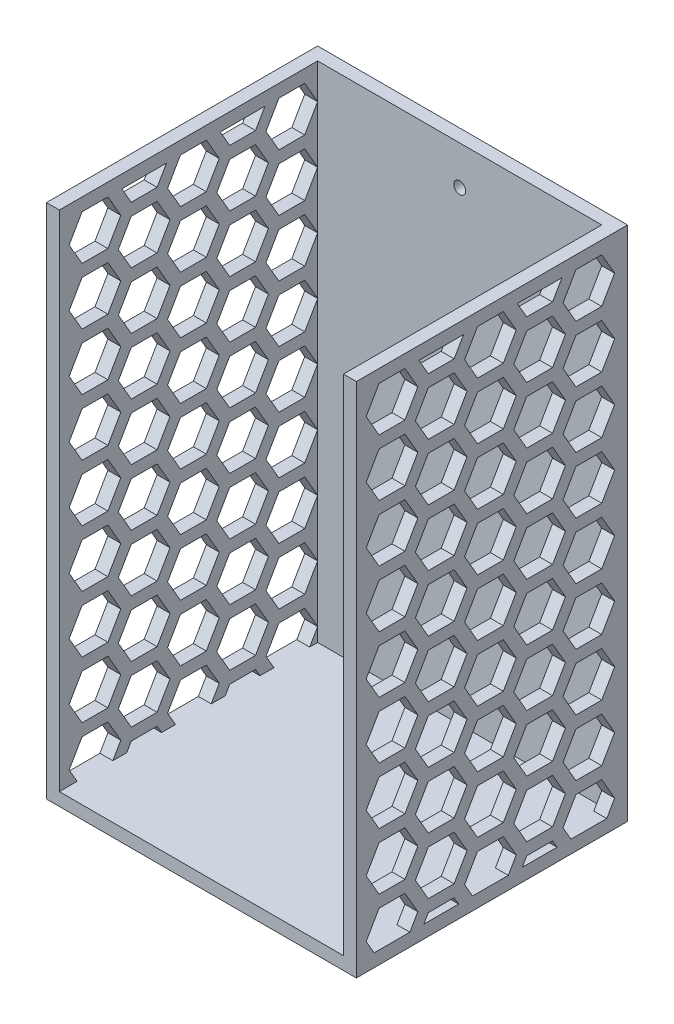
SolidWorks part; units mm, degrees
ref_plane "Front Plane" through (0, 0, 0) normal (0, 0, 1) x (1, 0, 0)
ref_plane "Top Plane" through (0, 0, 0) normal (0, 1, 0) x (1, 0, 0)
ref_plane "Right Plane" through (0, 0, 0) normal (1, 0, 0) x (0, 0, -1)
sketch "Sketch1" plane through (0, 0, 0) normal (0, 0, 1) x (1, 0, 0)
  line L1 (-60, -100) -> (60, -100)
  line L2 (-60, -100) -> (-60, 100)
  line L3 (-60, 100) -> (60, 100)
  line L4 (60, -100) -> (60, 100)
  line L5 (-60, -100) -> (60, 100) construction
  line L6 (-60, 100) -> (60, -100) construction
  point P0 (0, 0)
  dimension "D1" = 120
  dimension "D2" = 200
extrude "Boss-Extrude1" add sketch "Sketch1" along normal blind 5
sketch "Sketch2" plane through (0, 0, 0) normal (0, 0, 1) x (1, 0, 0)
  line L0 (60, 100) -> (-60, 100) construction
  line L1 (-60, -100) -> (60, -100) construction
  circle A0 centre (0, 85) radius 2.3
  circle A1 centre (0, -85) radius 2.3
  dimension "D1" = 4.6
  dimension "D2" = 15
  dimension "D3" = 15
extrude "Cut-Extrude2" cut sketch "Sketch2" along normal through all
sketch "Sketch3" plane through (0, 0, 5) normal (0, 0, 1) x (1, 0, 0)
  line L0 (-60, 100) -> (-60, -100) construction
  line L1 (-60, -95) -> (60, -95)
  line L2 (-60, -95) -> (-60, -100)
  line L3 (-60, -100) -> (60, -100)
  line L4 (60, -95) -> (60, -100)
  dimension "D1" = 5
extrude "Boss-Extrude2" add sketch "Sketch3" along normal blind 100
sketch "Sketch4" plane through (0, 0, 5) normal (0, 0, 1) x (1, 0, 0)
  line L0 (60, -95) -> (-60, -95) construction
  line L1 (-60, 100) -> (-55, 100)
  line L2 (-60, 100) -> (-60, -95)
  line L3 (-60, -95) -> (-55, -95)
  line L4 (-55, 100) -> (-55, -95)
  line L5 (60, -95) -> (-60, -95) construction
  line L6 (60, 100) -> (55, 100)
  line L7 (60, 100) -> (60, -95)
  line L8 (60, -95) -> (55, -95)
  line L9 (55, 100) -> (55, -95)
  dimension "D1" = 5
  dimension "D2" = 5
extrude "Boss-Extrude3" add sketch "Sketch4" along normal up to surface (100 mm away) up to face at (0, -97.5, 105)
sketch "Sketch5" plane through (-60, 0, 0) normal (-1, 0, 0) x (0, 0, 1)
  line L0 (20, -125) -> (10, -125)
  line L1 (20, 95) -> (10, 95)
  line L2 (10, 95) -> (5, 86.3397)
  line L3 (5, 86.3397) -> (10, 77.6795)
  line L4 (10, 77.6795) -> (20, 77.6795)
  line L5 (20, 77.6795) -> (25, 86.3397)
  line L6 (25, 86.3397) -> (20, 95)
  line L7 (0, 100) -> (0, -100) construction
  line L8 (39.0526, 106) -> (29.0526, 106)
  line L9 (29.0526, 106) -> (24.0526, 97.3397)
  line L10 (24.0526, 97.3397) -> (29.0526, 88.6795)
  line L11 (29.0526, 88.6795) -> (39.0526, 88.6795)
  line L12 (39.0526, 88.6795) -> (44.0526, 97.3397)
  line L13 (44.0526, 97.3397) -> (39.0526, 106)
  line L14 (58.1051, 117) -> (48.1051, 117)
  line L15 (48.1051, 117) -> (43.1051, 108.3397)
  line L16 (43.1051, 108.3397) -> (48.1051, 99.6795)
  line L17 (48.1051, 99.6795) -> (58.1051, 99.6795)
  line L18 (58.1051, 99.6795) -> (63.1051, 108.3397)
  line L19 (63.1051, 108.3397) -> (58.1051, 117)
  line L20 (77.1577, 128) -> (67.1577, 128)
  line L21 (67.1577, 128) -> (62.1577, 119.3397)
  line L22 (62.1577, 119.3397) -> (67.1577, 110.6795)
  line L23 (67.1577, 110.6795) -> (77.1577, 110.6795)
  line L24 (77.1577, 110.6795) -> (82.1577, 119.3397)
  line L25 (82.1577, 119.3397) -> (77.1577, 128)
  line L26 (96.2102, 139) -> (86.2102, 139)
  line L27 (86.2102, 139) -> (81.2102, 130.3397)
  line L28 (81.2102, 130.3397) -> (86.2102, 121.6795)
  line L29 (86.2102, 121.6795) -> (96.2102, 121.6795)
  line L30 (96.2102, 121.6795) -> (101.2102, 130.3397)
  line L31 (101.2102, 130.3397) -> (96.2102, 139)
  line L44 (39.0526, 84) -> (29.0526, 84)
  line L45 (29.0526, 84) -> (24.0526, 75.3397)
  line L46 (24.0526, 75.3397) -> (29.0526, 66.6795)
  line L47 (29.0526, 66.6795) -> (39.0526, 66.6795)
  line L48 (39.0526, 66.6795) -> (44.0526, 75.3397)
  line L49 (44.0526, 75.3397) -> (39.0526, 84)
  line L50 (58.1051, 95) -> (48.1051, 95)
  line L51 (48.1051, 95) -> (43.1051, 86.3397)
  line L52 (43.1051, 86.3397) -> (48.1051, 77.6795)
  line L53 (48.1051, 77.6795) -> (58.1051, 77.6795)
  line L54 (58.1051, 77.6795) -> (63.1051, 86.3397)
  line L55 (63.1051, 86.3397) -> (58.1051, 95)
  line L56 (77.1577, 106) -> (67.1577, 106)
  line L57 (67.1577, 106) -> (62.1577, 97.3397)
  line L58 (62.1577, 97.3397) -> (67.1577, 88.6795)
  line L59 (67.1577, 88.6795) -> (77.1577, 88.6795)
  line L60 (77.1577, 88.6795) -> (82.1577, 97.3397)
  line L61 (82.1577, 97.3397) -> (77.1577, 106)
  line L62 (96.2102, 117) -> (86.2102, 117)
  line L63 (86.2102, 117) -> (81.2102, 108.3397)
  line L64 (81.2102, 108.3397) -> (86.2102, 99.6795)
  line L65 (86.2102, 99.6795) -> (96.2102, 99.6795)
  line L66 (96.2102, 99.6795) -> (101.2102, 108.3397)
  line L67 (101.2102, 108.3397) -> (96.2102, 117)
  line L80 (39.0526, 62) -> (29.0526, 62)
  line L81 (29.0526, 62) -> (24.0526, 53.3397)
  line L82 (24.0526, 53.3397) -> (29.0526, 44.6795)
  line L83 (29.0526, 44.6795) -> (39.0526, 44.6795)
  line L84 (39.0526, 44.6795) -> (44.0526, 53.3397)
  line L85 (44.0526, 53.3397) -> (39.0526, 62)
  line L86 (58.1051, 73) -> (48.1051, 73)
  line L87 (48.1051, 73) -> (43.1051, 64.3397)
  line L88 (43.1051, 64.3397) -> (48.1051, 55.6795)
  line L89 (48.1051, 55.6795) -> (58.1051, 55.6795)
  line L90 (58.1051, 55.6795) -> (63.1051, 64.3397)
  line L91 (63.1051, 64.3397) -> (58.1051, 73)
  line L92 (77.1577, 84) -> (67.1577, 84)
  line L93 (67.1577, 84) -> (62.1577, 75.3397)
  line L94 (62.1577, 75.3397) -> (67.1577, 66.6795)
  line L95 (67.1577, 66.6795) -> (77.1577, 66.6795)
  line L96 (77.1577, 66.6795) -> (82.1577, 75.3397)
  line L97 (82.1577, 75.3397) -> (77.1577, 84)
  line L98 (96.2102, 95) -> (86.2102, 95)
  line L99 (86.2102, 95) -> (81.2102, 86.3397)
  line L100 (81.2102, 86.3397) -> (86.2102, 77.6795)
  line L101 (86.2102, 77.6795) -> (96.2102, 77.6795)
  line L102 (96.2102, 77.6795) -> (101.2102, 86.3397)
  line L103 (101.2102, 86.3397) -> (96.2102, 95)
  line L116 (39.0526, 40) -> (29.0526, 40)
  line L117 (29.0526, 40) -> (24.0526, 31.3397)
  line L118 (24.0526, 31.3397) -> (29.0526, 22.6795)
  line L119 (29.0526, 22.6795) -> (39.0526, 22.6795)
  line L120 (39.0526, 22.6795) -> (44.0526, 31.3397)
  line L121 (44.0526, 31.3397) -> (39.0526, 40)
  line L122 (58.1051, 51) -> (48.1051, 51)
  line L123 (48.1051, 51) -> (43.1051, 42.3397)
  line L124 (43.1051, 42.3397) -> (48.1051, 33.6795)
  line L125 (48.1051, 33.6795) -> (58.1051, 33.6795)
  line L126 (58.1051, 33.6795) -> (63.1051, 42.3397)
  line L127 (63.1051, 42.3397) -> (58.1051, 51)
  line L128 (77.1577, 62) -> (67.1577, 62)
  line L129 (67.1577, 62) -> (62.1577, 53.3397)
  line L130 (62.1577, 53.3397) -> (67.1577, 44.6795)
  line L131 (67.1577, 44.6795) -> (77.1577, 44.6795)
  line L132 (77.1577, 44.6795) -> (82.1577, 53.3397)
  line L133 (82.1577, 53.3397) -> (77.1577, 62)
  line L134 (96.2102, 73) -> (86.2102, 73)
  line L135 (86.2102, 73) -> (81.2102, 64.3397)
  line L136 (81.2102, 64.3397) -> (86.2102, 55.6795)
  line L137 (86.2102, 55.6795) -> (96.2102, 55.6795)
  line L138 (96.2102, 55.6795) -> (101.2102, 64.3397)
  line L139 (101.2102, 64.3397) -> (96.2102, 73)
  line L152 (39.0526, 18) -> (29.0526, 18)
  line L153 (29.0526, 18) -> (24.0526, 9.3397)
  line L154 (24.0526, 9.3397) -> (29.0526, 0.6795)
  line L155 (29.0526, 0.6795) -> (39.0526, 0.6795)
  line L156 (39.0526, 0.6795) -> (44.0526, 9.3397)
  line L157 (44.0526, 9.3397) -> (39.0526, 18)
  line L158 (58.1051, 29) -> (48.1051, 29)
  line L159 (48.1051, 29) -> (43.1051, 20.3397)
  line L160 (43.1051, 20.3397) -> (48.1051, 11.6795)
  line L161 (48.1051, 11.6795) -> (58.1051, 11.6795)
  line L162 (58.1051, 11.6795) -> (63.1051, 20.3397)
  line L163 (63.1051, 20.3397) -> (58.1051, 29)
  line L164 (77.1577, 40) -> (67.1577, 40)
  line L165 (67.1577, 40) -> (62.1577, 31.3397)
  line L166 (62.1577, 31.3397) -> (67.1577, 22.6795)
  line L167 (67.1577, 22.6795) -> (77.1577, 22.6795)
  line L168 (77.1577, 22.6795) -> (82.1577, 31.3397)
  line L169 (82.1577, 31.3397) -> (77.1577, 40)
  line L170 (96.2102, 51) -> (86.2102, 51)
  line L171 (86.2102, 51) -> (81.2102, 42.3397)
  line L172 (81.2102, 42.3397) -> (86.2102, 33.6795)
  line L173 (86.2102, 33.6795) -> (96.2102, 33.6795)
  line L174 (96.2102, 33.6795) -> (101.2102, 42.3397)
  line L175 (101.2102, 42.3397) -> (96.2102, 51)
  line L188 (39.0526, -4) -> (29.0526, -4)
  line L189 (29.0526, -4) -> (24.0526, -12.6603)
  line L190 (24.0526, -12.6603) -> (29.0526, -21.3205)
  line L191 (29.0526, -21.3205) -> (39.0526, -21.3205)
  line L192 (39.0526, -21.3205) -> (44.0526, -12.6603)
  line L193 (44.0526, -12.6603) -> (39.0526, -4)
  line L194 (58.1051, 7) -> (48.1051, 7)
  line L195 (48.1051, 7) -> (43.1051, -1.6603)
  line L196 (43.1051, -1.6603) -> (48.1051, -10.3205)
  line L197 (48.1051, -10.3205) -> (58.1051, -10.3205)
  line L198 (58.1051, -10.3205) -> (63.1051, -1.6603)
  line L199 (63.1051, -1.6603) -> (58.1051, 7)
  line L200 (77.1577, 18) -> (67.1577, 18)
  line L201 (67.1577, 18) -> (62.1577, 9.3397)
  line L202 (62.1577, 9.3397) -> (67.1577, 0.6795)
  line L203 (67.1577, 0.6795) -> (77.1577, 0.6795)
  line L204 (77.1577, 0.6795) -> (82.1577, 9.3397)
  line L205 (82.1577, 9.3397) -> (77.1577, 18)
  line L206 (96.2102, 29) -> (86.2102, 29)
  line L207 (86.2102, 29) -> (81.2102, 20.3397)
  line L208 (81.2102, 20.3397) -> (86.2102, 11.6795)
  line L209 (86.2102, 11.6795) -> (96.2102, 11.6795)
  line L210 (96.2102, 11.6795) -> (101.2102, 20.3397)
  line L211 (101.2102, 20.3397) -> (96.2102, 29)
  line L224 (39.0526, -26) -> (29.0526, -26)
  line L225 (29.0526, -26) -> (24.0526, -34.6603)
  line L226 (24.0526, -34.6603) -> (29.0526, -43.3205)
  line L227 (29.0526, -43.3205) -> (39.0526, -43.3205)
  line L228 (39.0526, -43.3205) -> (44.0526, -34.6603)
  line L229 (44.0526, -34.6603) -> (39.0526, -26)
  line L230 (58.1051, -15) -> (48.1051, -15)
  line L231 (48.1051, -15) -> (43.1051, -23.6603)
  line L232 (43.1051, -23.6603) -> (48.1051, -32.3205)
  line L233 (48.1051, -32.3205) -> (58.1051, -32.3205)
  line L234 (58.1051, -32.3205) -> (63.1051, -23.6603)
  line L235 (63.1051, -23.6603) -> (58.1051, -15)
  line L236 (77.1577, -4) -> (67.1577, -4)
  line L237 (67.1577, -4) -> (62.1577, -12.6603)
  line L238 (62.1577, -12.6603) -> (67.1577, -21.3205)
  line L239 (67.1577, -21.3205) -> (77.1577, -21.3205)
  line L240 (77.1577, -21.3205) -> (82.1577, -12.6603)
  line L241 (82.1577, -12.6603) -> (77.1577, -4)
  line L242 (96.2102, 7) -> (86.2102, 7)
  line L243 (86.2102, 7) -> (81.2102, -1.6603)
  line L244 (81.2102, -1.6603) -> (86.2102, -10.3205)
  line L245 (86.2102, -10.3205) -> (96.2102, -10.3205)
  line L246 (96.2102, -10.3205) -> (101.2102, -1.6603)
  line L247 (101.2102, -1.6603) -> (96.2102, 7)
  line L260 (39.0526, -48) -> (29.0526, -48)
  line L261 (29.0526, -48) -> (24.0526, -56.6603)
  line L262 (24.0526, -56.6603) -> (29.0526, -65.3205)
  line L263 (29.0526, -65.3205) -> (39.0526, -65.3205)
  line L264 (39.0526, -65.3205) -> (44.0526, -56.6603)
  line L265 (44.0526, -56.6603) -> (39.0526, -48)
  line L266 (58.1051, -37) -> (48.1051, -37)
  line L267 (48.1051, -37) -> (43.1051, -45.6603)
  line L268 (43.1051, -45.6603) -> (48.1051, -54.3205)
  line L269 (48.1051, -54.3205) -> (58.1051, -54.3205)
  line L270 (58.1051, -54.3205) -> (63.1051, -45.6603)
  line L271 (63.1051, -45.6603) -> (58.1051, -37)
  line L272 (77.1577, -26) -> (67.1577, -26)
  line L273 (67.1577, -26) -> (62.1577, -34.6603)
  line L274 (62.1577, -34.6603) -> (67.1577, -43.3205)
  line L275 (67.1577, -43.3205) -> (77.1577, -43.3205)
  line L276 (77.1577, -43.3205) -> (82.1577, -34.6603)
  line L277 (82.1577, -34.6603) -> (77.1577, -26)
  line L278 (96.2102, -15) -> (86.2102, -15)
  line L279 (86.2102, -15) -> (81.2102, -23.6603)
  line L280 (81.2102, -23.6603) -> (86.2102, -32.3205)
  line L281 (86.2102, -32.3205) -> (96.2102, -32.3205)
  line L282 (96.2102, -32.3205) -> (101.2102, -23.6603)
  line L283 (101.2102, -23.6603) -> (96.2102, -15)
  line L296 (39.0526, -70) -> (29.0526, -70)
  line L297 (29.0526, -70) -> (24.0526, -78.6603)
  line L298 (24.0526, -78.6603) -> (29.0526, -87.3205)
  line L299 (29.0526, -87.3205) -> (39.0526, -87.3205)
  line L300 (39.0526, -87.3205) -> (44.0526, -78.6603)
  line L301 (44.0526, -78.6603) -> (39.0526, -70)
  line L302 (58.1051, -59) -> (48.1051, -59)
  line L303 (48.1051, -59) -> (43.1051, -67.6603)
  line L304 (43.1051, -67.6603) -> (48.1051, -76.3205)
  line L305 (48.1051, -76.3205) -> (58.1051, -76.3205)
  line L306 (58.1051, -76.3205) -> (63.1051, -67.6603)
  line L307 (63.1051, -67.6603) -> (58.1051, -59)
  line L308 (77.1577, -48) -> (67.1577, -48)
  line L309 (67.1577, -48) -> (62.1577, -56.6603)
  line L310 (62.1577, -56.6603) -> (67.1577, -65.3205)
  line L311 (67.1577, -65.3205) -> (77.1577, -65.3205)
  line L312 (77.1577, -65.3205) -> (82.1577, -56.6603)
  line L313 (82.1577, -56.6603) -> (77.1577, -48)
  line L314 (96.2102, -37) -> (86.2102, -37)
  line L315 (86.2102, -37) -> (81.2102, -45.6603)
  line L316 (81.2102, -45.6603) -> (86.2102, -54.3205)
  line L317 (86.2102, -54.3205) -> (96.2102, -54.3205)
  line L318 (96.2102, -54.3205) -> (101.2102, -45.6603)
  line L319 (101.2102, -45.6603) -> (96.2102, -37)
  line L332 (39.0526, -92) -> (29.0526, -92)
  line L333 (29.0526, -92) -> (24.0526, -100.6603)
  line L334 (24.0526, -100.6603) -> (29.0526, -109.3205)
  line L335 (29.0526, -109.3205) -> (39.0526, -109.3205)
  line L336 (39.0526, -109.3205) -> (44.0526, -100.6603)
  line L337 (44.0526, -100.6603) -> (39.0526, -92)
  line L338 (58.1051, -81) -> (48.1051, -81)
  line L339 (48.1051, -81) -> (43.1051, -89.6603)
  line L340 (43.1051, -89.6603) -> (48.1051, -98.3205)
  line L341 (48.1051, -98.3205) -> (58.1051, -98.3205)
  line L342 (58.1051, -98.3205) -> (63.1051, -89.6603)
  line L343 (63.1051, -89.6603) -> (58.1051, -81)
  line L344 (77.1577, -70) -> (67.1577, -70)
  line L345 (67.1577, -70) -> (62.1577, -78.6603)
  line L346 (62.1577, -78.6603) -> (67.1577, -87.3205)
  line L347 (67.1577, -87.3205) -> (77.1577, -87.3205)
  line L348 (77.1577, -87.3205) -> (82.1577, -78.6603)
  line L349 (82.1577, -78.6603) -> (77.1577, -70)
  line L350 (96.2102, -59) -> (86.2102, -59)
  line L351 (86.2102, -59) -> (81.2102, -67.6603)
  line L352 (81.2102, -67.6603) -> (86.2102, -76.3205)
  line L353 (86.2102, -76.3205) -> (96.2102, -76.3205)
  line L354 (96.2102, -76.3205) -> (101.2102, -67.6603)
  line L355 (101.2102, -67.6603) -> (96.2102, -59)
  line L512 (20, 73) -> (10, 73)
  line L513 (10, 73) -> (5, 64.3397)
  line L514 (5, 64.3397) -> (10, 55.6795)
  line L515 (10, 55.6795) -> (20, 55.6795)
  line L516 (20, 55.6795) -> (25, 64.3397)
  line L517 (25, 64.3397) -> (20, 73)
  line L518 (20, 51) -> (10, 51)
  line L519 (10, 51) -> (5, 42.3397)
  line L520 (5, 42.3397) -> (10, 33.6795)
  line L521 (10, 33.6795) -> (20, 33.6795)
  line L522 (20, 33.6795) -> (25, 42.3397)
  line L523 (25, 42.3397) -> (20, 51)
  line L524 (20, 29) -> (10, 29)
  line L525 (10, 29) -> (5, 20.3397)
  line L526 (5, 20.3397) -> (10, 11.6795)
  line L527 (10, 11.6795) -> (20, 11.6795)
  line L528 (20, 11.6795) -> (25, 20.3397)
  line L529 (25, 20.3397) -> (20, 29)
  line L530 (20, 7) -> (10, 7)
  line L531 (10, 7) -> (5, -1.6603)
  line L532 (5, -1.6603) -> (10, -10.3205)
  line L533 (10, -10.3205) -> (20, -10.3205)
  line L534 (20, -10.3205) -> (25, -1.6603)
  line L535 (25, -1.6603) -> (20, 7)
  line L536 (20, -15) -> (10, -15)
  line L537 (10, -15) -> (5, -23.6603)
  line L538 (5, -23.6603) -> (10, -32.3205)
  line L539 (10, -32.3205) -> (20, -32.3205)
  line L540 (20, -32.3205) -> (25, -23.6603)
  line L541 (25, -23.6603) -> (20, -15)
  line L542 (20, -37) -> (10, -37)
  line L543 (10, -37) -> (5, -45.6603)
  line L544 (5, -45.6603) -> (10, -54.3205)
  line L545 (10, -54.3205) -> (20, -54.3205)
  line L546 (20, -54.3205) -> (25, -45.6603)
  line L547 (25, -45.6603) -> (20, -37)
  line L548 (20, -59) -> (10, -59)
  line L549 (10, -59) -> (5, -67.6603)
  line L550 (5, -67.6603) -> (10, -76.3205)
  line L551 (10, -76.3205) -> (20, -76.3205)
  line L552 (20, -76.3205) -> (25, -67.6603)
  line L553 (25, -67.6603) -> (20, -59)
  line L554 (20, -81) -> (10, -81)
  line L555 (10, -81) -> (5, -89.6603)
  line L556 (5, -89.6603) -> (10, -98.3205)
  line L557 (10, -98.3205) -> (20, -98.3205)
  line L558 (20, -98.3205) -> (25, -89.6603)
  line L559 (25, -89.6603) -> (20, -81)
  line L560 (20, -103) -> (10, -103)
  line L561 (10, -103) -> (5, -111.6603)
  line L562 (5, -111.6603) -> (10, -120.3205)
  line L563 (10, -120.3205) -> (20, -120.3205)
  line L564 (20, -120.3205) -> (25, -111.6603)
  line L565 (25, -111.6603) -> (20, -103)
  line L590 (20, 95) -> (39.0526, 106) construction
  line L591 (105, 100) -> (0, 100) construction
  line L592 (10, -125) -> (5, -133.6603)
  line L593 (5, -133.6603) -> (10, -142.3205)
  line L594 (10, -142.3205) -> (20, -142.3205)
  line L595 (20, -142.3205) -> (25, -133.6603)
  line L596 (25, -133.6603) -> (20, -125)
  line L597 (39.0526, -114) -> (29.0526, -114)
  line L598 (29.0526, -114) -> (24.0526, -122.6603)
  line L599 (24.0526, -122.6603) -> (29.0526, -131.3205)
  line L600 (29.0526, -131.3205) -> (39.0526, -131.3205)
  line L601 (39.0526, -131.3205) -> (44.0526, -122.6603)
  line L602 (44.0526, -122.6603) -> (39.0526, -114)
  line L603 (58.1051, -103) -> (48.1051, -103)
  line L604 (48.1051, -103) -> (43.1051, -111.6603)
  line L605 (43.1051, -111.6603) -> (48.1051, -120.3205)
  line L606 (48.1051, -120.3205) -> (58.1051, -120.3205)
  line L607 (58.1051, -120.3205) -> (63.1051, -111.6603)
  line L608 (63.1051, -111.6603) -> (58.1051, -103)
  line L609 (77.1577, -92) -> (67.1577, -92)
  line L610 (67.1577, -92) -> (62.1577, -100.6603)
  line L611 (62.1577, -100.6603) -> (67.1577, -109.3205)
  line L612 (67.1577, -109.3205) -> (77.1577, -109.3205)
  line L613 (77.1577, -109.3205) -> (82.1577, -100.6603)
  line L614 (82.1577, -100.6603) -> (77.1577, -92)
  line L615 (96.2102, -81) -> (86.2102, -81)
  line L616 (86.2102, -81) -> (81.2102, -89.6603)
  line L617 (81.2102, -89.6603) -> (86.2102, -98.3205)
  line L618 (86.2102, -98.3205) -> (96.2102, -98.3205)
  line L619 (96.2102, -98.3205) -> (101.2102, -89.6603)
  line L620 (101.2102, -89.6603) -> (96.2102, -81)
  line L621 (20, -147) -> (10, -147)
  line L622 (10, -147) -> (5, -155.6603)
  line L623 (5, -155.6603) -> (10, -164.3205)
  line L624 (10, -164.3205) -> (20, -164.3205)
  line L625 (20, -164.3205) -> (25, -155.6603)
  line L626 (25, -155.6603) -> (20, -147)
  line L627 (39.0526, -136) -> (29.0526, -136)
  line L628 (29.0526, -136) -> (24.0526, -144.6603)
  line L629 (24.0526, -144.6603) -> (29.0526, -153.3205)
  line L630 (29.0526, -153.3205) -> (39.0526, -153.3205)
  line L631 (39.0526, -153.3205) -> (44.0526, -144.6603)
  line L632 (44.0526, -144.6603) -> (39.0526, -136)
  line L633 (58.1051, -125) -> (48.1051, -125)
  line L634 (48.1051, -125) -> (43.1051, -133.6603)
  line L635 (43.1051, -133.6603) -> (48.1051, -142.3205)
  line L636 (48.1051, -142.3205) -> (58.1051, -142.3205)
  line L637 (58.1051, -142.3205) -> (63.1051, -133.6603)
  line L638 (63.1051, -133.6603) -> (58.1051, -125)
  line L639 (77.1577, -114) -> (67.1577, -114)
  line L640 (67.1577, -114) -> (62.1577, -122.6603)
  line L641 (62.1577, -122.6603) -> (67.1577, -131.3205)
  line L642 (67.1577, -131.3205) -> (77.1577, -131.3205)
  line L643 (77.1577, -131.3205) -> (82.1577, -122.6603)
  line L644 (82.1577, -122.6603) -> (77.1577, -114)
  line L645 (96.2102, -103) -> (86.2102, -103)
  line L646 (86.2102, -103) -> (81.2102, -111.6603)
  line L647 (81.2102, -111.6603) -> (86.2102, -120.3205)
  line L648 (86.2102, -120.3205) -> (96.2102, -120.3205)
  line L649 (96.2102, -120.3205) -> (101.2102, -111.6603)
  line L650 (101.2102, -111.6603) -> (96.2102, -103)
  line L651 (20, -169) -> (10, -169)
  line L652 (10, -169) -> (5, -177.6603)
  line L653 (5, -177.6603) -> (10, -186.3205)
  line L654 (10, -186.3205) -> (20, -186.3205)
  line L655 (20, -186.3205) -> (25, -177.6603)
  line L656 (25, -177.6603) -> (20, -169)
  line L657 (39.0526, -158) -> (29.0526, -158)
  line L658 (29.0526, -158) -> (24.0526, -166.6603)
  line L659 (24.0526, -166.6603) -> (29.0526, -175.3205)
  line L660 (29.0526, -175.3205) -> (39.0526, -175.3205)
  line L661 (39.0526, -175.3205) -> (44.0526, -166.6603)
  line L662 (44.0526, -166.6603) -> (39.0526, -158)
  line L663 (58.1051, -147) -> (48.1051, -147)
  line L664 (48.1051, -147) -> (43.1051, -155.6603)
  line L665 (43.1051, -155.6603) -> (48.1051, -164.3205)
  line L666 (48.1051, -164.3205) -> (58.1051, -164.3205)
  line L667 (58.1051, -164.3205) -> (63.1051, -155.6603)
  line L668 (63.1051, -155.6603) -> (58.1051, -147)
  line L669 (77.1577, -136) -> (67.1577, -136)
  line L670 (67.1577, -136) -> (62.1577, -144.6603)
  line L671 (62.1577, -144.6603) -> (67.1577, -153.3205)
  line L672 (67.1577, -153.3205) -> (77.1577, -153.3205)
  line L673 (77.1577, -153.3205) -> (82.1577, -144.6603)
  line L674 (82.1577, -144.6603) -> (77.1577, -136)
  line L675 (96.2102, -125) -> (86.2102, -125)
  line L676 (86.2102, -125) -> (81.2102, -133.6603)
  line L677 (81.2102, -133.6603) -> (86.2102, -142.3205)
  line L678 (86.2102, -142.3205) -> (96.2102, -142.3205)
  line L679 (96.2102, -142.3205) -> (101.2102, -133.6603)
  line L680 (101.2102, -133.6603) -> (96.2102, -125)
  circle A0 centre (15, 86.3397) radius 8.6603 construction
  dimension "D1" = 10
  dimension "D2" = 5
  dimension "D3" = 15
  dimension "D6" = 22
  dimension "D4" = 5
  dimension "D5" = 13
extrude "Cut-Extrude3" cut sketch "Sketch5" against normal through all
sketch "Sketch6" plane through (-60, 0, 0) normal (-1, 0, 0) x (0, 0, 1)
  line L0 (105, 100) -> (105, -100)
  line L1 (0, 100) -> (105, 100)
  line L2 (0, 100) -> (0, 95)
  line L3 (0, 95) -> (102, 95)
  line L5 (0, -100) -> (105, -100)
  line L6 (0, -100) -> (0, -95)
  line L7 (0, -95) -> (102, -95)
  line L12 (102, 95) -> (102, -95)
  line L13 (105, 100) -> (105, -100) construction
  point P1 (0, 0)
  point P14 (0, 0)
  dimension "D1" = 5
  dimension "D2" = 3
  dimension "D3" = 5
extrude "Boss-Extrude4" add sketch "Sketch6" against normal up to surface (5 mm away) up to face at (-55, 53.3397, 72.1577)
sketch "Sketch7" plane through (60, 0, 0) normal (1, 0, 0) x (0, 0, -1)
  line L1 (0, -100) -> (-105, -100)
  line L2 (0, -100) -> (0, -95)
  line L3 (0, -95) -> (-105, -95)
  line L4 (-105, -100) -> (-105, -95)
  point P7 (0, 0)
  dimension "D1" = 5
extrude "Boss-Extrude5" add sketch "Sketch7" against normal up to surface (120 mm away) up to face at (-60, -88.5534, 15)
sketch "Sketch8" plane through (60, 0, 0) normal (1, 0, 0) x (0, 0, -1)
  line L5 (-105, 100) -> (-105, -100)
  line L10 (0, 100) -> (-105, 100)
  line L11 (0, 100) -> (0, 95)
  line L12 (0, 95) -> (-102, 95)
  line L14 (-105, -100) -> (-105, 100) construction
  line L15 (-105, -100) -> (-102, -100)
  line L16 (-102, -100) -> (-102, 95)
  line L17 (-105, -100) -> (0, -100) construction
  point P9 (-104.7477, 100)
  point P17 (0, 0)
  dimension "D1" = 3
extrude "Boss-Extrude6" add sketch "Sketch8" against normal up to surface (5 mm away) up to face at (55, 53.3397, 72.1577)
